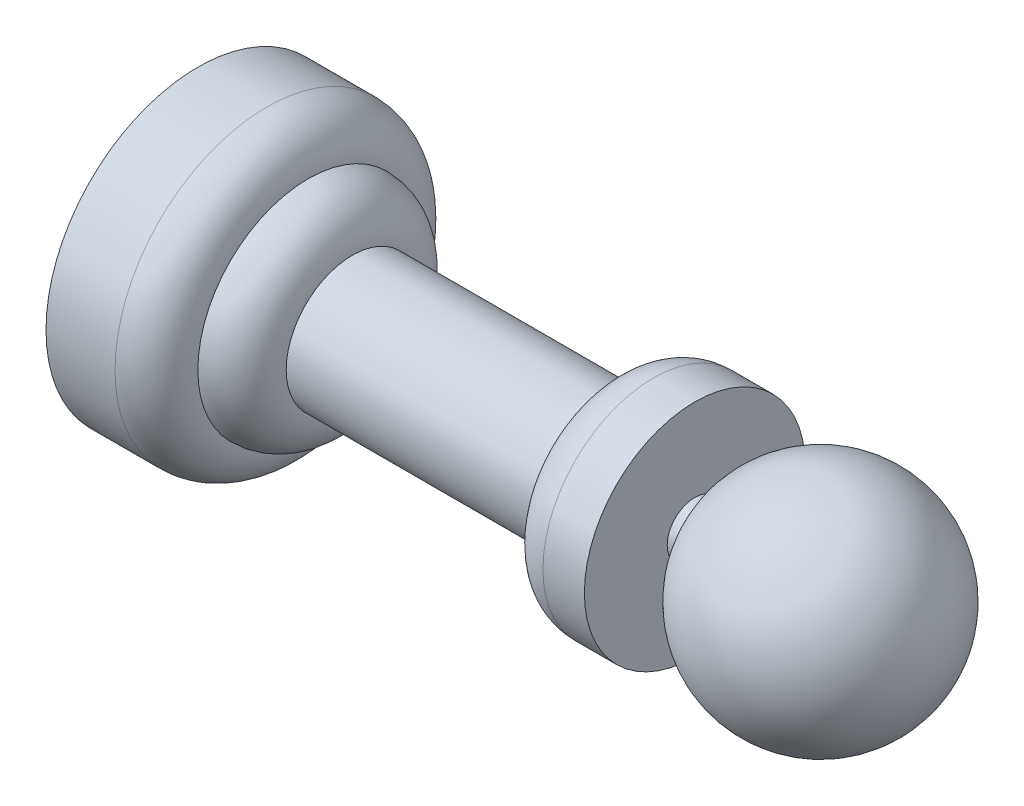
SolidWorks part; units mm, degrees
ref_plane "Спереди" through (0, 0, 0) normal (0, 0, 1) x (1, 0, 0)
ref_plane "Сверху" through (0, 0, 0) normal (0, 1, 0) x (1, 0, 0)
ref_plane "Справа" through (0, 0, 0) normal (1, 0, 0) x (0, 0, -1)
other "Configuration Table"
sketch "Эскиз2" plane through (0, 0, 0) normal (0, 0, 1) x (1, 0, 0)
  line L0 (0, 11) -> (61.8612, 11) construction
  line L1 (0, 0) -> (5, 0)
  line L2 (0, 0) -> (0, 22)
  line L3 (0, 22) -> (5, 22)
  line L4 (5, 0) -> (5, 22)
  line L5 (5, 19) -> (8, 19)
  line L6 (5, 19) -> (5, 3)
  line L7 (5, 3) -> (8, 3)
  line L8 (8, 19) -> (8, 3)
  line L9 (8, 15.8) -> (33, 15.8)
  line L10 (8, 15.8) -> (8, 6.2)
  line L11 (8, 6.2) -> (33, 6.2)
  line L12 (33, 15.8) -> (33, 6.2)
  line L13 (33, 3) -> (36, 3)
  line L14 (33, 3) -> (33, 19)
  line L15 (33, 19) -> (36, 19)
  line L16 (36, 3) -> (36, 19)
  line L17 (36, 13) -> (37.2708, 13)
  line L18 (36, 13) -> (36, 9)
  line L19 (36, 9) -> (37.2708, 9)
  arc A0 (5, 0) -> (8, 3) centre (5, 3) ccw
  arc A1 (8, 3) -> (11.2, 6.2) centre (8, 6.2) ccw
  arc A2 (33, 3) -> (29.8, 6.2) centre (33, 6.2) cw
  circle A3 centre (45.0979, 11) radius 8.0786
  dimension "D8" = 3
  dimension "D9" = 3.2
  dimension "D15" = 3.2
  dimension "D19" = 12.0979
  dimension "D16" = 16.1572
  dimension "D1" = 22
  dimension "D2" = 5
  dimension "D3" = 3
  dimension "D4" = 3
  dimension "D5" = 3
  dimension "D6" = 3.2
  dimension "D7" = 3.2
  dimension "D10" = 25
  dimension "D11" = 3.2
  dimension "D12" = 3
  dimension "D13" = 16
  dimension "D14" = 25
  dimension "D17" = 4
  dimension "D18" = 6
revolve "Повернуть7" add sketch "Эскиз2" angle 360 about L0 region at (2.5, 5.5, 0) region at (6.5, 7, 0) region at (20.5, 8.6, 0) region at (6.2732, 1.7268, 0) region at (34.5, 7, 0) region at (9.3581, 4.8419, 0) region at (36.5538, 9.9621, 0) region at (31.6419, 4.8419, 0) region at (45.0979, 7.5713, 0)
sketch "Эскиз3" plane through (0, 0, 0) normal (-1, 0, 0) x (0, 0, 1)
  line L0 (7.3426, 2.8094) -> (-7.3426, 19.1906) construction
  line L1 (-10.6948, 8.4267) -> (10.6948, 13.5733) construction
  circle A0 centre (0, 11) radius 10
  circle A1 centre (0, 11) radius 11 construction
  point P8 (0, 11)
  dimension "D1" = 20
extrude "Вырез-Вытянуть1" cut sketch "Эскиз3" against normal blind 2.5
